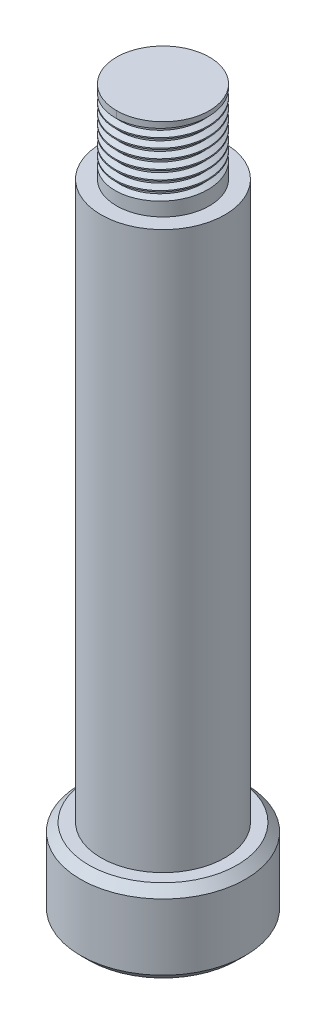
SolidWorks part; units mm, degrees
material "AISI Type A2 Tool Steel"
ref_plane "Front Plane" through (0, 0, 0) normal (0, 0, 1) x (1, 0, 0)
ref_plane "Top Plane" through (0, 0, 0) normal (0, 1, 0) x (1, 0, 0)
ref_plane "Right Plane" through (0, 0, 0) normal (1, 0, 0) x (0, 0, -1)
sketch "Sketch2" plane through (0, 0, 0) normal (0, 1, 0) x (1, 0, 0)
  circle A0 centre (0, 0) radius 12.7
  dimension "D1" = 25.4
extrude "Boss-Extrude1" add sketch "Sketch2" along normal blind 12.7
sketch "Sketch3" plane through (0, 12.7, 0) normal (0, 1, 0) x (1, 0, 0)
  circle A0 centre (0, 0) radius 9.525
  dimension "D1" = 19.05
extrude "Boss-Extrude2" add sketch "Sketch3" along normal blind 98.425
ref_plane "Plane1" through (0, 97.79, 0) normal (0, 1, 0) x (1, 0, 0)
sketch "Sketch4" plane through (0, 97.79, 0) normal (0, 1, 0) x (1, 0, 0)
  circle A0 centre (0, 0) radius 9.525 construction
  dimension "D1" = 19.05
sketch "Sketch5" plane through (0, 0, 0) normal (0, 0, 1) x (1, 0, 0)
  line L0 (0, 97.79) -> (-9.525, 97.79) construction
  line L1 (9.525, 97.79) -> (-9.525, 97.79) construction
  line L2 (-9.525, 97.155) -> (-9.525, 98.425) construction
  line L3 (-9.525, 98.425) -> (-8.001, 98.425)
  line L4 (-8.001, 98.425) -> (-8.001, 97.155)
  line L5 (-8.001, 97.155) -> (-9.525, 97.155)
  line L6 (-9.525, 97.155) -> (-10.0615, 97.155)
  line L7 (-10.0615, 97.155) -> (-10.0615, 98.425)
  line L8 (-10.0615, 98.425) -> (-9.525, 98.425)
  line L9 (0, 97.79) -> (0, 103.732) construction
  point P10 (-9.525, 97.79)
  dimension "D1" = 1.27
  dimension "D2" = 1.524
  dimension "D3" = 8.001
  dimension "D4" = 10.0615
revolve "Cut-Revolve1" [suppressed] cut sketch "Sketch5" angle 360 about L9
sketch "Sketch9" plane through (0, 111.125, 0) normal (0, 1, 0) x (1, 0, 0)
  circle A0 centre (0, 0) radius 12.7
  circle A1 centre (0, 0) radius 7.1438
  dimension "D1" = 14.2875
  dimension "D2" = 25.4
extrude "Cut-Extrude1" cut sketch "Sketch9" against normal blind 12.7
thread "Thread2" pitch 1.4111 method cut profile "Thread Profile2" start angle 0, offset 0, length 10, pitch 1.4111, diameter 14.2875
ref_plane "Plane3" through (-7.1438, 111.125, 0) normal (0, 0, 1) x (-1, 0, 0)
sketch "Thread Profile2" plane through (-7.1438, 111.125, 0) normal (0, 0, 1) x (-1, 0, 0)
  line L0 (0, 0) -> (0, 1.4111) construction
  line L11 (0, 0) -> (0, 1.2347)
  line L12 (0, 1.2347) -> (-0.7638, 0.7937)
  line L13 (-0.7638, 0.7937) -> (-0.7638, 0.441)
  line L15 (-0.7638, 0.441) -> (0, 0)
  line L17 (-0.7638, 0.6174) -> (0, 0.6174) construction
  point P2 (0, 0)
  dimension "Pitch" = 1.4111
  dimension "Profile_Angle" = 60
  dimension "Profile_Land" = 0.3528
  dimension "Profile_Height" = 0.7638
chamfer "Chamfer1" distance 1.27 1 edges at (0, 0, 12.7)
chamfer "Chamfer2" distance 1.27 angle 45 1 edges at (0, 12.7, 12.7)
sketch "Sketch10" plane through (0, 0, 0) normal (0, -1, 0) x (1, 0, 0)
  line L1 (0, 5.4993) -> (-4.7625, 2.7496)
  line L2 (-4.7625, 2.7496) -> (-4.7625, -2.7496)
  line L3 (-4.7625, -2.7496) -> (0, -5.4993)
  line L4 (0, -5.4993) -> (4.7625, -2.7496)
  line L5 (4.7625, -2.7496) -> (4.7625, 2.7496)
  line L6 (4.7625, 2.7496) -> (0, 5.4993)
  circle A0 centre (0, 0) radius 4.7625 construction
  dimension "D1" = 9.525
extrude "Cut-Extrude2" cut sketch "Sketch10" against normal blind 9.525
sketch "Sketch11" plane through (0, 0, 0) normal (1, 0, 0) x (0, 0, -1)
  line L0 (0, 9.3418) -> (0, -9.3418) construction
  point P4 (0, 0)
ref_plane "Plane4" through (0, 1.27, 0) normal (0, -1, 0) x (-1, 0, 0)
